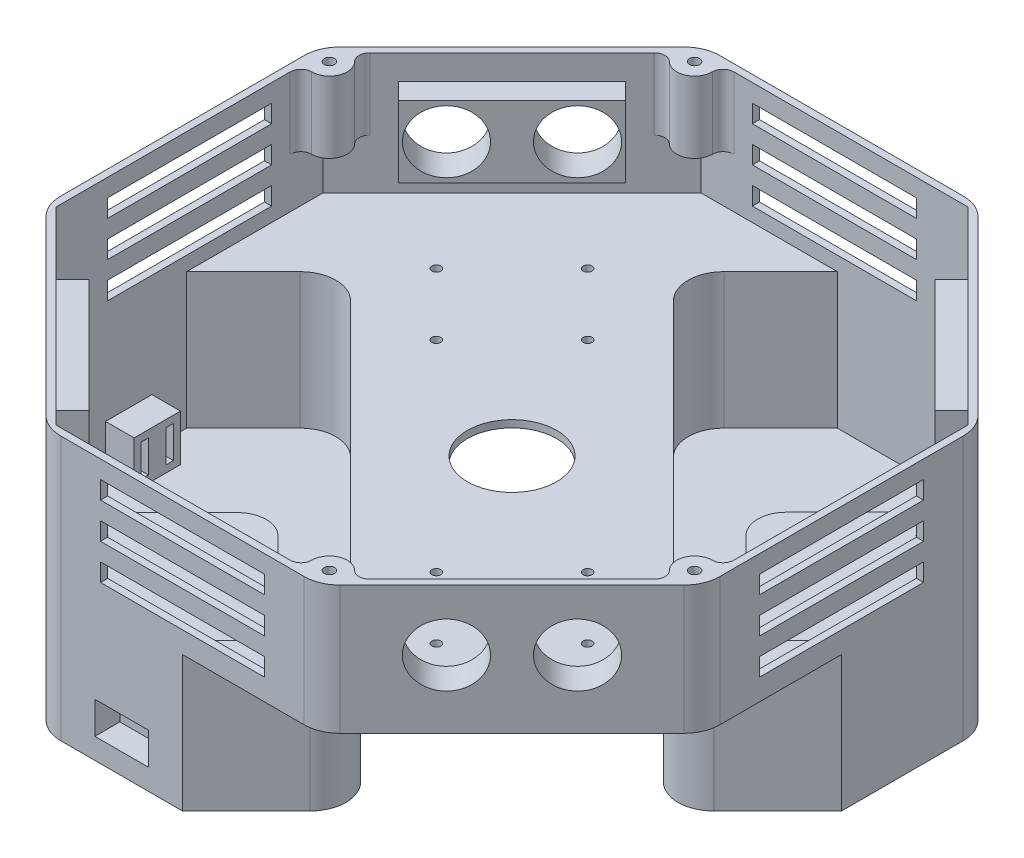
SolidWorks part; units mm, degrees
ref_plane "Front Plane" through (0, 0, 0) normal (0, 0, 1) x (1, 0, 0)
ref_plane "Top Plane" through (0, 0, 0) normal (0, 1, 0) x (1, 0, 0)
ref_plane "Right Plane" through (0, 0, 0) normal (1, 0, 0) x (0, 0, -1)
sketch "Sketch1" plane through (0, 0, 0) normal (0, 1, 0) x (1, 0, 0)
  line L7 (92.388, -38.2683) -> (92.388, 38.2683)
  line L8 (92.388, 38.2683) -> (38.2683, 92.388)
  line L9 (38.2683, 92.388) -> (-38.2683, 92.388)
  line L10 (-38.2683, 92.388) -> (-92.388, 38.2683)
  line L11 (-92.388, 38.2683) -> (-92.388, -38.2683)
  line L12 (-92.388, -38.2683) -> (-38.2683, -92.388)
  line L13 (-38.2683, -92.388) -> (38.2683, -92.388)
  line L14 (38.2683, -92.388) -> (92.388, -38.2683)
  circle A0 centre (0, 0) radius 92.388 construction
  dimension "D1" = 200
sketch "Sketch2" plane through (0, 0, 0) normal (0, 0, 1) x (1, 0, 0)
  line L0 (0, 0) -> (0, 74)
  point P3 (0, 61)
  point P4 (0, 41)
  point P5 (0, 38)
  point P10 (0, 71)
  dimension "D1" = 38
  dimension "D2" = 3
  dimension "D3" = 20
  dimension "D4" = 10
  dimension "D5" = 3
extrude "Boss-Extrude1" add sketch "Sketch1" along normal up to vertex (74 mm away) contours L13 L14 L7 L8 L9 L10 L11 L12 up to point (0, 74, 0)
sketch "Sketch3" plane through (0, 0, 0) normal (0, -1, 0) x (1, 0, 0)
  line L0 (-86.5414, -44.1149) -> (44.1149, 86.5414)
  line L1 (-38.2683, -92.388) -> (-92.388, -38.2683) construction
  line L2 (38.2683, 92.388) -> (92.388, 38.2683) construction
  line L3 (-44.1149, -86.5414) -> (86.5414, 44.1149)
  line L4 (-65.3281, -65.3281) -> (65.3281, 65.3281) construction
  line L5 (-86.5414, -44.1149) -> (-44.1149, -86.5414)
  line L6 (44.1149, 86.5414) -> (86.5414, 44.1149)
  dimension "D1" = 60
extrude "Cut-Extrude1" cut sketch "Sketch3" against normal blind 38
sketch "Sketch4" plane through (0, 0, 0) normal (0, -1, 0) x (1, 0, 0)
  line L0 (-92.388, -38.2683) -> (-86.5414, -44.1149) construction
  line L1 (-86.5414, -44.1149) -> (44.1149, 86.5414) construction
  line L2 (44.1149, 86.5414) -> (38.2683, 92.388) construction
  line L3 (38.2683, 92.388) -> (-38.2683, 92.388) construction
  line L4 (-38.2683, 92.388) -> (-92.388, 38.2683) construction
  line L5 (-92.388, 38.2683) -> (-92.388, -38.2683) construction
  line L6 (92.388, 38.2683) -> (86.5414, 44.1149) construction
  line L7 (86.5414, 44.1149) -> (-44.1149, -86.5414) construction
  line L8 (-44.1149, -86.5414) -> (-38.2683, -92.388) construction
  line L9 (-38.2683, -92.388) -> (38.2683, -92.388) construction
  line L10 (38.2683, -92.388) -> (92.388, -38.2683) construction
  line L11 (92.388, -38.2683) -> (92.388, 38.2683) construction
  line L12 (-92.388, -38.2683) -> (-86.5414, -44.1149)
  line L13 (-86.5414, -44.1149) -> (44.1149, 86.5414)
  line L14 (44.1149, 86.5414) -> (38.2683, 92.388)
  line L15 (38.2683, 92.388) -> (-38.2683, 92.388)
  line L16 (-38.2683, 92.388) -> (-92.388, 38.2683)
  line L17 (-92.388, 38.2683) -> (-92.388, -38.2683)
  line L18 (92.388, 38.2683) -> (86.5414, 44.1149)
  line L19 (86.5414, 44.1149) -> (-44.1149, -86.5414)
  line L20 (-44.1149, -86.5414) -> (-38.2683, -92.388)
  line L21 (-38.2683, -92.388) -> (38.2683, -92.388)
  line L22 (38.2683, -92.388) -> (92.388, -38.2683)
  line L23 (92.388, -38.2683) -> (92.388, 38.2683)
extrude "Cut-Extrude2" [suppressed] cut sketch "Sketch4" against normal blind 38
sketch "Sketch5" plane through (0, 0, 0) normal (0, -1, 0) x (1, 0, 0)
  line L12 (-49.0647, 70.2779) -> (-49.0647, 27.8515) construction
  line L13 (53.3073, -74.5205) -> (74.5205, -53.3073)
  line L14 (74.5205, -44.8221) -> (53.3073, -23.6088)
  line L15 (44.8221, -23.6088) -> (23.6088, -44.8221)
  line L16 (23.6088, -53.3073) -> (44.8221, -74.5205)
  line L17 (38.2683, -92.388) -> (92.388, -38.2683) construction
  line L18 (65.3281, -65.3281) -> (21.2132, -21.2132) construction
  line L19 (86.5414, 44.1149) -> (-44.1149, -86.5414) construction
  line L20 (65.3281, 65.3281) -> (-65.3281, -65.3281) construction
  line L21 (86.5414, 44.1149) -> (44.1149, 86.5414) construction
  line L22 (-86.5414, -44.1149) -> (-44.1149, -86.5414) construction
  line L23 (53.3073, -23.6088) -> (74.5205, -44.8221)
  line L24 (44.8221, -74.5205) -> (23.6088, -53.3073)
  line L25 (-65.3281, 65.3281) -> (-21.2132, 21.2132) construction
  line L26 (-74.5205, 44.8221) -> (-53.3073, 23.6088)
  line L27 (-23.6088, 53.3073) -> (-44.8221, 74.5205)
  line L28 (-53.3073, 23.6088) -> (-74.5205, 44.8221)
  line L29 (-23.6088, 44.8221) -> (-44.8221, 23.6088)
  line L30 (-44.8221, 74.5205) -> (-23.6088, 53.3073)
  line L31 (-74.5205, 53.3073) -> (-53.3073, 74.5205)
  line L32 (49.0647, -27.8515) -> (49.0647, -70.2779) construction
  arc A0 (44.8221, -74.5205) -> (53.3073, -74.5205) centre (49.0647, -70.2779) ccw
  arc A1 (74.5205, -53.3073) -> (74.5205, -44.8221) centre (70.2779, -49.0647) ccw
  arc A2 (53.3073, -23.6088) -> (44.8221, -23.6088) centre (49.0647, -27.8515) ccw
  arc A3 (23.6088, -44.8221) -> (23.6088, -53.3073) centre (27.8515, -49.0647) ccw
  arc A4 (44.8221, -23.6088) -> (53.3073, -23.6088) centre (49.0647, -27.8515) cw
  arc A5 (23.6088, -53.3073) -> (23.6088, -44.8221) centre (27.8515, -49.0647) cw
  arc A6 (53.3073, -74.5205) -> (44.8221, -74.5205) centre (49.0647, -70.2779) cw
  arc A7 (74.5205, -44.8221) -> (74.5205, -53.3073) centre (70.2779, -49.0647) cw
  arc A8 (-44.8221, 74.5205) -> (-53.3073, 74.5205) centre (-49.0647, 70.2779) ccw
  arc A9 (-74.5205, 53.3073) -> (-74.5205, 44.8221) centre (-70.2779, 49.0647) ccw
  arc A10 (-53.3073, 23.6088) -> (-44.8221, 23.6088) centre (-49.0647, 27.8515) ccw
  arc A11 (-23.6088, 44.8221) -> (-23.6088, 53.3073) centre (-27.8515, 49.0647) ccw
  arc A12 (-44.8221, 23.6088) -> (-53.3073, 23.6088) centre (-49.0647, 27.8515) cw
  arc A13 (-23.6088, 53.3073) -> (-23.6088, 44.8221) centre (-27.8515, 49.0647) cw
  arc A14 (-53.3073, 74.5205) -> (-44.8221, 74.5205) centre (-49.0647, 70.2779) cw
  arc A15 (-74.5205, 44.8221) -> (-74.5205, 53.3073) centre (-70.2779, 49.0647) cw
  point P12 (49.0647, -78.7632)
  point P15 (78.7632, -49.0647)
  point P20 (19.3662, -49.0647)
  point P41 (-49.0647, 19.3662)
  point P42 (-49.0647, 78.7632)
  point P43 (-78.7632, 49.0647)
  point P44 (43.2707, -43.2707)
  dimension "D4" = 6
  dimension "D1" = 42
  dimension "D2" = 42
  dimension "D5" = 5.794
extrude "Cut-Extrude3" cut sketch "Sketch5" against normal blind 8 contours L29 A11 L27 A8 L31 A9 L26 A10 region at (-49.0647, 0, 49.0647)
sketch "Sketch6" plane through (0, 38, 0) normal (0, -1, 0) x (1, 0, 0)
  line L0 (65.3281, 65.3281) -> (-65.3281, -65.3281)
  line L1 (86.5414, 44.1149) -> (44.1149, 86.5414) construction
  line L2 (-86.5414, -44.1149) -> (-44.1149, -86.5414) construction
sketch "Sketch7" plane through (0, 8, 0) normal (0, -1, 0) x (1, 0, 0)
  line L0 (-63.9139, 63.9139) -> (65.3281, -65.3281)
  line L1 (-74.5205, 53.3073) -> (-53.3073, 74.5205) construction
  line L2 (38.2683, -92.388) -> (92.388, -38.2683) construction
sketch "Sketch8" plane through (0, 0, 0) normal (0, -1, 0) x (1, 0, 0)
  line L0 (53.3073, -74.5205) -> (74.5205, -53.3073) construction
  line L1 (44.8221, -23.6088) -> (23.6088, -44.8221) construction
  line L2 (23.6088, -53.3073) -> (44.8221, -74.5205) construction
  line L3 (74.5205, -44.8221) -> (53.3073, -23.6088) construction
  line L4 (53.3073, -74.5205) -> (74.5205, -53.3073)
  line L5 (44.8221, -23.6088) -> (23.6088, -44.8221)
  line L6 (23.6088, -53.3073) -> (44.8221, -74.5205)
  line L7 (74.5205, -44.8221) -> (53.3073, -23.6088)
  arc A0 (74.5205, -53.3073) -> (74.5205, -44.8221) centre (70.2779, -49.0647) ccw construction
  arc A1 (44.8221, -74.5205) -> (53.3073, -74.5205) centre (49.0647, -70.2779) ccw construction
  arc A2 (23.6088, -44.8221) -> (23.6088, -53.3073) centre (27.8515, -49.0647) ccw construction
  arc A3 (53.3073, -23.6088) -> (44.8221, -23.6088) centre (49.0647, -27.8515) ccw construction
  arc A4 (74.5205, -53.3073) -> (74.5205, -44.8221) centre (70.2779, -49.0647) ccw
  arc A5 (44.8221, -74.5205) -> (53.3073, -74.5205) centre (49.0647, -70.2779) ccw
  arc A6 (23.6088, -44.8221) -> (23.6088, -53.3073) centre (27.8515, -49.0647) ccw
  arc A7 (53.3073, -23.6088) -> (44.8221, -23.6088) centre (49.0647, -27.8515) ccw
  point P12 (-29.9728, 51.186)
  point P13 (0, 32.0941)
  point P15 (-51.186, 29.9728)
  point P17 (-46.9434, 68.1566)
  point P19 (-68.1566, 46.9434)
extrude "Cut-Extrude4" cut sketch "Sketch8" against normal blind 8.1
sketch "Sketch9" plane through (0, 0, 0) normal (0, -1, 0) x (1, 0, 0)
  line L0 (0, 92.388) -> (92.388, 0)
  line L1 (38.2683, 92.388) -> (-38.2683, 92.388) construction
  line L2 (92.388, -38.2683) -> (92.388, 38.2683) construction
  line L3 (92.388, 0) -> (117.9869, 25.599)
  line L4 (117.9869, 25.599) -> (39.2649, 104.3211)
  line L5 (39.2649, 104.3211) -> (0, 92.388)
  line L6 (0, -92.388) -> (-92.388, 0)
  line L7 (-38.2683, -92.388) -> (38.2683, -92.388) construction
  line L8 (-92.388, 38.2683) -> (-92.388, -38.2683) construction
  line L9 (-92.388, 0) -> (-117.9869, -25.599)
  line L10 (-117.9869, -25.599) -> (-25.599, -117.9869)
  line L11 (-25.599, -117.9869) -> (0, -92.388)
extrude "Cut-Extrude5" cut sketch "Sketch9" against normal up to surface (38 mm away) up to face at (0, 38, 0)
shell "Shell2" thickness 2 removed face at (0, 74, 0)
sketch "Sketch10" plane through (63.9139, 0, -63.9139) normal (-0.7071, 0, 0.7071) x (0.7071, 0, 0.7071)
  line L0 (0, 67) -> (0, 47) construction
  line L1 (-22.5, 47) -> (22.5, 47) construction
  line L2 (-22.5, 47) -> (-22.5, 67) construction
  line L3 (-22.5, 67) -> (22.5, 67) construction
  line L4 (22.5, 47) -> (22.5, 67) construction
  line L5 (-22.5, 47) -> (22.5, 67) construction
  line L6 (-22.5, 67) -> (22.5, 47) construction
  line L7 (25.9975, 74.2342) -> (25.9975, 39.7658) construction
  line L8 (-37.4399, 74) -> (-37.4399, 40) construction
  line L9 (-37.4399, 74) -> (-37.4399, 2) construction
  line L10 (-63.3281, 40) -> (63.3281, 40) construction
  line L11 (-37.4399, 74) -> (37.4399, 74) construction
  circle A0 centre (13, 57) radius 8.75
  circle A1 centre (-13, 57) radius 8.75
  point P0 (0, 57)
  point P13 (25.9975, 57)
  point P15 (-37.4399, 57)
  point P16 (0, 74)
  dimension "D3" = 17.5
  dimension "D1" = 20
  dimension "D2" = 45
  dimension "D4" = 26
sketch "Sketch11" plane through (63.9139, 0, -63.9139) normal (-0.7071, 0, 0.7071) x (0.7071, 0, 0.7071)
  line L0 (-22.5, 47) -> (22.5, 47) construction
  line L1 (22.5, 47) -> (22.5, 67) construction
  line L2 (-22.5, 67) -> (22.5, 67) construction
  line L3 (-22.5, 47) -> (-22.5, 67) construction
  line L4 (-22.5, 47) -> (22.5, 47)
  line L5 (22.5, 47) -> (22.5, 67)
  line L6 (-22.5, 67) -> (22.5, 67)
  line L7 (-22.5, 47) -> (-22.5, 67)
extrude "Boss-Extrude2" add sketch "Sketch11" along normal blind 6.5
sketch "Sketch12" plane through (59.3177, 0, -59.3177) normal (-0.7071, 0, 0.7071) x (0.7071, 0, 0.7071)
  circle A0 centre (-13, 57) radius 8.75 construction
  circle A1 centre (13, 57) radius 8.75 construction
  circle A2 centre (-13, 57) radius 8.75
  circle A3 centre (13, 57) radius 8.75
extrude "Cut-Extrude6" cut sketch "Sketch12" against normal through all contours A2 | A3 region at (50.1254, 57, -68.5101)
mirror "Mirror1" about plane through (0, 0, 0) normal (1, 0, 0) of "Cut-Extrude6", "Boss-Extrude2"
mirror "Mirror2" about plane through (0, 0, 0) normal (0, 0, 1) of "Mirror1"
sketch "Sketch13" plane through (0, 74, 0) normal (0, 1, 0) x (1, 0, 0)
  line L0 (-37.4399, 90.388) -> (37.4399, -90.388) construction
  line L1 (38.2683, -92.388) -> (92.388, -38.2683) construction
  circle A1 centre (36.1973, -87.388) radius 5
  circle A2 centre (0, 0) radius 25.9051 construction
  circle A3 centre (-36.1973, -87.388) radius 5 construction
  circle A4 centre (-87.388, -36.1973) radius 5 construction
  circle A5 centre (-87.388, 36.1973) radius 5
  circle A6 centre (-36.1973, 87.388) radius 5
  circle A7 centre (36.1973, 87.388) radius 5 construction
  circle A8 centre (87.388, 36.1973) radius 5 construction
  circle A9 centre (87.388, -36.1973) radius 5
  point P26 (0, 0)
  dimension "D1" = 10
  dimension "D2" = 8
extrude "Boss-Extrude3" add sketch "Sketch13" against normal blind 20
fillet "Fillet2" radius 3 8 edges at (-86.6808, 64, -41.147) (32.1973, 64, 90.388) (41.147, 64, 86.6808) (86.6808, 64, 41.147) (90.388, 64, 32.1973) (-41.147, 64, -86.6808) (-32.1973, 64, -90.388) (-90.388, 64, -32.1973)
sketch "Sketch14" plane through (0, 74, 0) normal (0, 1, 0) x (1, 0, 0)
  point P0 (-87.388, 36.1973)
  point P1 (-36.1973, 87.388)
  point P3 (36.1973, -87.388)
  point P5 (87.388, -36.1973)
hole_wizard "M3.5x0.6 Tapped Hole1" positions "Sketch14" profile "Sketch15" tap size "M3.5x0.6" standard "ANSI Metric"
sketch "Sketch15" plane through (-87.388, 74, -36.1973) normal (1, 0, 0) x (0, 0, 1)
  line L0 (0, 0) -> (0, 10.8712)
  line L1 (0, 10.8712) -> (1.45, 10)
  line L2 (1.45, 10) -> (1.45, 0)
  line L5 (1.45, 0) -> (0, 0)
  line L10 (0, 10.8712) -> (-1.45, 10) construction
  line L11 (0, -6.35) -> (0, 107.95) construction
  dimension "Tap Drill Dia." = 2.9
  dimension "Tap Drill Depth" = 10
  dimension "Drill Angle" = 118
cosmetic thread "Hole Thread1" parameters "D1"=7, "D2"=3.5
cosmetic thread "Hole Thread2" parameters "D1"=7, "D2"=3.5
cosmetic thread "Hole Thread3" parameters "D1"=7, "D2"=3.5
cosmetic thread "Hole Thread4" parameters "D1"=7, "D2"=3.5
fillet "Fillet5" radius 10 12 edges at (38.2683, 37, -92.388) (92.388, 37, -38.2683) (92.388, 56, 38.2683) (38.2683, 56, 92.388) (-38.2683, 56, -92.388) (-92.388, 56, -38.2683) (-92.388, 37, 38.2683) (-38.2683, 37, 92.388) (-67.4072, 19, -24.9808) (-24.9808, 19, -67.4072) (67.4072, 19, 24.9808) (24.9808, 19, 67.4072)
sketch "Sketch16" plane through (0, 0, 0) normal (0, -1, 0) x (1, 0, 0)
  line L0 (41.1973, -89.459) -> (-0.8882, -43.3146)
  line L1 (-17.9097, -60.3361) -> (60.3361, 17.9097) construction
  line L2 (-0.8882, -43.3146) -> (23.6088, -44.8221)
  line L3 (23.6088, -44.8221) -> (21.2132, -21.2132)
  line L4 (-17.9097, -60.3361) -> (60.3361, 17.9097) construction
  line L5 (21.2132, -21.2132) -> (44.8221, -23.6088)
  line L6 (44.8221, -23.6088) -> (47.7588, 5.3324)
  line L7 (47.7588, 5.3324) -> (89.6938, -27.298)
  arc A0 (89.459, -41.1973) -> (92.388, -34.1262) centre (82.388, -34.1262) ccw construction
sketch "Sketch17" plane through (0, 0, 0) normal (0, -1, 0) x (1, 0, 0)
  line L0 (24.1702, -78.2018) -> (31.2413, -85.2729) construction
  line L1 (31.2413, -85.2729) -> (38.3123, -78.2018) construction
  line L2 (38.3123, -78.2018) -> (31.2413, -71.1307) construction
  line L3 (31.2413, -71.1307) -> (24.1702, -78.2018) construction
  line L4 (41.1973, -89.459) -> (-0.8882, -43.3146) construction
  line L5 (38.2683, -92.388) -> (92.388, -38.2683) construction
  line L6 (31.2413, -68.3023) -> (21.3418, -78.2018) construction
  line L7 (21.3418, -78.2018) -> (31.2413, -88.1013) construction
  line L8 (31.2413, -88.1013) -> (41.1408, -78.2018) construction
  line L9 (41.1408, -78.2018) -> (31.2413, -68.3023) construction
  line L10 (-63.9139, 63.9139) -> (65.3281, -65.3281) construction
  line L11 (-63.9139, 63.9139) -> (65.3281, -65.3281) construction
  line L12 (71.1307, -31.2413) -> (78.2018, -24.1702) construction
  line L13 (78.2018, -38.3123) -> (71.1307, -31.2413) construction
  line L14 (85.2729, -31.2413) -> (78.2018, -38.3123) construction
  line L15 (78.2018, -24.1702) -> (85.2729, -31.2413) construction
  line L16 (78.2018, -41.1408) -> (68.3023, -31.2413)
  line L17 (88.1013, -31.2413) -> (78.2018, -41.1408)
  line L18 (78.2018, -21.3418) -> (88.1013, -31.2413)
  line L19 (68.3023, -31.2413) -> (78.2018, -21.3418)
  point P2 (27.7057, -74.6663)
  dimension "D1" = 10
  dimension "D2" = 10
  dimension "D3" = 10
  dimension "D4" = 2
extrude "Boss-Extrude4" add sketch "Sketch17" against normal blind 8
sketch "Sketch18" plane through (0, 0, 0) normal (0, -1, 0) x (1, 0, 0)
  line L0 (78.2018, -22.756) -> (69.7165, -31.2413)
  line L1 (69.7165, -31.2413) -> (78.2018, -39.7266)
  line L2 (78.2018, -39.7266) -> (86.6871, -31.2413)
  line L3 (86.6871, -31.2413) -> (78.2018, -22.756)
  line L4 (68.3023, -31.2413) -> (78.2018, -41.1408)
  line L5 (78.2018, -21.3418) -> (68.3023, -31.2413)
  line L6 (88.1013, -31.2413) -> (78.2018, -21.3418)
  line L7 (78.2018, -41.1408) -> (88.1013, -31.2413)
  line L8 (68.3023, -31.2413) -> (78.2018, -41.1408) construction
  line L9 (78.2018, -21.3418) -> (68.3023, -31.2413) construction
  line L10 (88.1013, -31.2413) -> (78.2018, -21.3418) construction
  line L11 (78.2018, -41.1408) -> (88.1013, -31.2413) construction
  dimension "D1" = 0
  dimension "D2" = 1
extrude "Cut-Extrude7" cut sketch "Sketch18" against normal blind 5
sketch "Sketch19" plane through (0, 5, 0) normal (0, -1, 0) x (1, 0, 0)
  line L0 (71.1307, -32.6555) -> (79.616, -24.1702)
  line L1 (85.2729, -29.8271) -> (76.7876, -38.3123)
  line L2 (79.616, -24.1702) -> (78.2018, -22.756)
  line L3 (76.7876, -38.3123) -> (78.2018, -39.7266)
  line L4 (86.6871, -31.2413) -> (78.2018, -22.756)
  line L5 (78.2018, -22.756) -> (69.7165, -31.2413)
  line L6 (69.7165, -31.2413) -> (78.2018, -39.7266)
  line L7 (78.2018, -39.7266) -> (86.6871, -31.2413)
  line L8 (86.6871, -31.2413) -> (85.2729, -29.8271)
  line L9 (78.2018, -22.756) -> (69.7165, -31.2413)
  line L10 (69.7165, -31.2413) -> (71.1307, -32.6555)
  line L11 (78.2018, -39.7266) -> (86.6871, -31.2413)
  dimension "D1" = 0
  dimension "D2" = 2
  dimension "D3" = 2
extrude "Cut-Extrude8" cut sketch "Sketch19" against normal through all
sketch "Sketch20" plane through (-65.3281, 0, 65.3281) normal (-0.7071, 0, 0.7071) x (0.7071, 0, 0.7071)
  line L0 (-38.2683, 0) -> (38.2683, 0) construction
  circle A0 centre (21.8233, 23.5) radius 8.5 construction
  circle A1 centre (21.8233, 23.5) radius 5.5 construction
  circle A2 centre (21.8233, 23.5) radius 10.5
  point P2 (21.8233, 15)
  dimension "D1" = 15
  dimension "D2" = 17
  dimension "D3" = 11
  dimension "D4" = 2
extrude "Boss-Extrude5" add sketch "Sketch20" against normal blind 6
sketch "Sketch21" plane through (-65.3281, 0, 65.3281) normal (-0.7071, 0, 0.7071) x (0.7071, 0, 0.7071)
  circle A0 centre (21.8233, 23.5) radius 8.5 construction
  circle A1 centre (21.8233, 23.5) radius 8.5
extrude "Cut-Extrude9" cut sketch "Sketch21" against normal blind 3
sketch "Sketch22" plane through (-63.2068, 0, 63.2068) normal (-0.7071, 0, 0.7071) x (0.7071, 0, 0.7071)
  circle A0 centre (21.8233, 23.5) radius 5.5 construction
  circle A1 centre (21.8233, 23.5) radius 5.5
extrude "Cut-Extrude10" cut sketch "Sketch22" against normal blind 3
sketch "Sketch23" plane through (65.3281, 0, -65.3281) normal (0.7071, 0, -0.7071) x (-0.7071, 0, -0.7071)
  arc A0 (-21.75, 32.0046) -> (20.5971, 32.0046) centre (-0.5764, 27.0304) ccw
  arc A1 (-21.75, 32.0046) -> (20.5971, 32.0046) centre (-0.5764, 52.4388) ccw
  circle A2 centre (-13, 57) radius 8.75 construction
  circle A3 centre (-13, 57) radius 8.75 construction
  circle A4 centre (13, 57) radius 8.75 construction
  point P8 (-21.75, 57)
  point P10 (20.5971, 61.3412)
extrude "Cut-Extrude11" cut sketch "Sketch23" against normal blind 0.5
sketch "Sketch24" plane through (-65.3281, 0, 65.3281) normal (-0.7071, 0, 0.7071) x (0.7071, 0, 0.7071)
  circle A0 centre (-18.9113, 18.5) radius 5.25
  point P0 (21.8233, 23.5)
  dimension "D1" = 10.5
extrude "Boss-Extrude6" add sketch "Sketch24" against normal blind 11
sketch "Sketch25" plane through (-65.3281, 0, 65.3281) normal (-0.7071, 0, 0.7071) x (0.7071, 0, 0.7071)
  circle A0 centre (-18.9113, 18.5) radius 3.25
  circle A1 centre (-18.9113, 18.5) radius 5.25
  circle A2 centre (-18.9113, 18.5) radius 5.25 construction
  dimension "D2" = 2
  dimension "D1" = 0
extrude "Cut-Extrude12" cut sketch "Sketch25" against normal blind 8
sketch "Sketch26" plane through (-59.6713, 0, 59.6713) normal (-0.7071, 0, 0.7071) x (0.7071, 0, 0.7071)
  line L1 (-20.2999, 21.4384) -> (-20.2999, 15.5616)
  line L4 (-17.5228, 21.4384) -> (-17.5228, 15.5616)
  circle A3 centre (-18.9113, 18.5) radius 3.25 construction
  arc A4 (-20.2999, 21.4384) -> (-20.2999, 15.5616) centre (-18.9113, 18.5) ccw
  arc A5 (-17.5228, 15.5616) -> (-17.5228, 21.4384) centre (-18.9113, 18.5) ccw
extrude "Cut-Extrude13" cut sketch "Sketch26" against normal blind 6
sketch "Sketch29" plane through (0, 8, 0) normal (0, -1, 0) x (1, 0, 0)
  point P20 (68.1566, -46.9434)
  point P23 (51.186, -29.9728)
  point P26 (29.9728, -51.186)
  point P29 (46.9434, -68.1566)
  point P32 (-51.186, 29.9728)
  point P35 (-68.1566, 46.9434)
  point P38 (-29.9728, 51.186)
  point P41 (-46.9434, 68.1566)
  point P44 (0, 0)
hole_wizard "M3x0.5 Tapped Hole1" positions "Sketch29" profile "Sketch30" tap size "M3x0.5" standard "ANSI Metric"
cosmetic thread "Hole Thread7" parameters "D1"=64, "D2"=3
cosmetic thread "Hole Thread8" parameters "D1"=64, "D2"=3
cosmetic thread "Hole Thread9" parameters "D1"=64, "D2"=3
cosmetic thread "Hole Thread10" parameters "D1"=64, "D2"=3
cosmetic thread "Hole Thread11" parameters "D1"=64, "D2"=3
cosmetic thread "Hole Thread12" parameters "D1"=64, "D2"=3
sketch "Sketch30" plane through (68.1566, 8, -46.9434) normal (1, 0, 0) x (0, 0, -1)
  line L0 (0, 0) -> (0, 2.8511)
  line L1 (0, 2.8511) -> (1.25, 2.1)
  line L2 (1.25, 2.1) -> (1.25, 0)
  line L5 (1.25, 0) -> (0, 0)
  line L10 (0, 2.8511) -> (-1.25, 2.1) construction
  line L11 (0, -6.35) -> (0, 107.95) construction
  dimension "Tap Drill Dia." = 2.5
  dimension "Tap Drill Depth" = 2.1
  dimension "Drill Angle" = 118
cosmetic thread "Hole Thread21" parameters "D1"=64, "D2"=3
cosmetic thread "Hole Thread22" parameters "D1"=64, "D2"=3
sketch "Sketch31" plane through (0, 38, 0) normal (0, -1, 0) x (1, 0, 0)
  line L0 (-43.7426, -86.9137) -> (86.9137, 43.7426)
  line L1 (-86.9137, -43.7426) -> (43.7426, 86.9137)
  line L2 (-86.9137, -43.7426) -> (-43.7426, -86.9137)
  line L3 (43.7426, 86.9137) -> (86.9137, 43.7426)
  line L4 (34.9226, 56.1358) -> (56.1358, 34.9226) construction
  line L5 (-86.9137, -43.7426) -> (86.9137, 43.7426) construction
  line L6 (45.5292, 45.5292) -> (65.3281, 65.3281) construction
  line L7 (-89.459, 41.1973) -> (-41.1973, 89.459) construction
  line L8 (89.459, 41.1973) -> (41.1973, 89.459) construction
  line L9 (-21.5855, 21.5855) -> (21.5855, -21.5855) construction
  circle A2 centre (34.9226, 56.1358) radius 1.74
  circle A3 centre (56.1358, 34.9226) radius 1.74
  circle A4 centre (17.5984, 38.8116) radius 1.74
  circle A5 centre (38.8116, 17.5984) radius 1.74
  circle A6 centre (-56.1358, -34.9226) radius 1.74
  circle A7 centre (-34.9226, -56.1358) radius 1.74
  circle A8 centre (-17.5984, -38.8116) radius 1.74
  circle A9 centre (-38.8116, -17.5984) radius 1.74
  point P4 (65.3281, 65.3281)
  point P5 (45.5292, 45.5292)
  point P14 (0, 0)
  dimension "D10" = 3.48
  dimension "D2" = 2
  dimension "D3" = 28
  dimension "D4" = 0
  dimension "D6" = 15.5266
  dimension "D9" = 30
sketch "Sketch32" plane through (0, 38, 0) normal (0, -1, 0) x (1, 0, 0)
  point P0 (-56.1358, -34.9226)
  point P1 (-38.8116, -17.5984)
  point P3 (-17.5984, -38.8116)
  point P5 (-34.9226, -56.1358)
  point P7 (38.8116, 17.5984)
  point P9 (56.1358, 34.9226)
  point P11 (34.9226, 56.1358)
  point P13 (17.5984, 38.8116)
hole_wizard "M3x0.5 Tapped Hole2" positions "Sketch32" profile "Sketch33" tap size "M3x0.5" standard "ANSI Metric" end condition through all
sketch "Sketch33" plane through (-56.1358, 38, -34.9226) normal (1, 0, 0) x (0, 0, -1)
  line L0 (0, 0) -> (0, 36)
  line L1 (0, 36) -> (1.25, 36)
  line L2 (1.25, 36) -> (1.25, 0)
  line L5 (1.25, 0) -> (0, 0)
  line L11 (0, -6.35) -> (0, 107.95) construction
  dimension "Thru Tap Drill Dia." = 2.5
  dimension "Thru Tap Drill Depth" = 36
cosmetic thread "Hole Thread13" parameters "D2"=3
cosmetic thread "Hole Thread14" parameters "D2"=3
cosmetic thread "Hole Thread15" parameters "D2"=3
cosmetic thread "Hole Thread16" parameters "D2"=3
cosmetic thread "Hole Thread17" parameters "D2"=3
cosmetic thread "Hole Thread18" parameters "D2"=3
cosmetic thread "Hole Thread19" parameters "D2"=3
cosmetic thread "Hole Thread20" parameters "D2"=3
sketch "Sketch34" plane through (0, 38, 0) normal (0, -1, 0) x (1, 0, 0)
  circle A1 centre (0, 0) radius 12.5
  dimension "D1" = 25
extrude "Cut-Extrude14" cut sketch "Sketch34" against normal through all
sketch "Sketch35" plane through (92.388, 0, 0) normal (1, 0, 0) x (0, 0, -1)
  line L0 (0, 37.0336) -> (0, 90.07) construction
  line L1 (-23, 59) -> (23, 59)
  line L2 (-23, 64) -> (23, 64)
  line L3 (-23, 64) -> (-23, 69)
  line L4 (-23, 69) -> (23, 69)
  line L5 (23, 64) -> (23, 69)
  line L6 (-23, 64) -> (23, 69) construction
  line L7 (-23, 69) -> (23, 64) construction
  line L8 (-23, 54) -> (-23, 59)
  line L9 (-23, 54) -> (23, 54)
  line L10 (23, 54) -> (23, 59)
  line L11 (-23, 59) -> (23, 54) construction
  line L12 (-23, 54) -> (23, 59) construction
  line L13 (-23, 49) -> (23, 49)
  line L14 (-23, 44) -> (-23, 49)
  line L15 (-23, 44) -> (23, 44)
  line L16 (23, 44) -> (23, 49)
  line L17 (-23, 49) -> (23, 44) construction
  line L18 (-23, 44) -> (23, 49) construction
  line L19 (90.388, 74) -> (-90.388, 74) construction
  line L20 (17.9097, 0) -> (17.9097, 38) construction
  line L21 (-65.3281, 38) -> (65.3281, 38) construction
  line L22 (7.9097, 21.25) -> (27.9097, 21.25) construction
  line L23 (7.9097, 28.75) -> (27.9097, 28.75) construction
  line L24 (7.9097, 28.75) -> (7.9097, 31.75) construction
  line L25 (7.9097, 31.75) -> (27.9097, 31.75) construction
  line L26 (27.9097, 28.75) -> (27.9097, 31.75) construction
  line L27 (7.9097, 28.75) -> (27.9097, 31.75) construction
  line L28 (7.9097, 31.75) -> (27.9097, 28.75) construction
  line L29 (7.9097, 24.25) -> (27.9097, 24.25) construction
  line L30 (27.9097, 21.25) -> (27.9097, 24.25) construction
  line L31 (7.9097, 21.25) -> (7.9097, 24.25) construction
  line L32 (7.9097, 24.25) -> (27.9097, 21.25) construction
  line L33 (7.9097, 21.25) -> (27.9097, 24.25) construction
  line L34 (7.9097, 13.75) -> (27.9097, 13.75) construction
  line L35 (7.9097, 16.75) -> (27.9097, 16.75) construction
  line L36 (27.9097, 13.75) -> (27.9097, 16.75) construction
  line L37 (7.9097, 13.75) -> (7.9097, 16.75) construction
  line L38 (7.9097, 16.75) -> (27.9097, 13.75) construction
  line L39 (7.9097, 13.75) -> (27.9097, 16.75) construction
  line L40 (7.9097, 6.25) -> (27.9097, 6.25) construction
  line L41 (7.9097, 9.25) -> (27.9097, 9.25) construction
  line L42 (27.9097, 6.25) -> (27.9097, 9.25) construction
  line L43 (7.9097, 6.25) -> (7.9097, 9.25) construction
  line L44 (7.9097, 9.25) -> (27.9097, 6.25) construction
  line L45 (7.9097, 6.25) -> (27.9097, 9.25) construction
  line L46 (27.9097, 21.25) -> (27.9097, 16.75) construction
  point P2 (0, 66.5)
  point P23 (17.9097, 30.25)
  point P29 (17.9097, 19)
  point P41 (27.9097, 19)
  dimension "D1" = 46
  dimension "D2" = 5
  dimension "D3" = 5
  dimension "D4" = 3
  dimension "D5" = 20
  dimension "5" = 5
  dimension "D8" = 5
  dimension "D6" = 4
extrude "Cut-Extrude15" cut sketch "Sketch35" against normal up to next
ref_plane "Plane1" through (0, 0, 0) normal (0.7071, 0, 0.7071) x (0.7071, 0, -0.7071)
mirror "Mirror3" about plane through (0, 0, 0) normal (0.7071, 0, 0.7071) of "Cut-Extrude15"
ref_plane "Plane2" through (0, 0, 0) normal (-0.7071, 0, 0.7071) x (0.7071, 0, 0.7071)
mirror "Mirror4" about plane through (0, 0, 0) normal (-0.7071, 0, 0.7071) of "Mirror3", "Cut-Extrude15"
sketch "Sketch37" plane through (0, 0, 92.388) normal (0, 0, 1) x (1, 0, 0)
  line L0 (-17.0631, 0) -> (-17.0631, 38.9532) construction
  line L1 (-23.5631, 6.8582) -> (-10.5631, 6.8582) construction
  line L2 (-23.5631, 6.8582) -> (-23.5631, 13.8582) construction
  line L3 (-23.5631, 13.8582) -> (-10.5631, 13.8582) construction
  line L4 (-10.5631, 6.8582) -> (-10.5631, 13.8582) construction
  line L5 (-23.5631, 6.8582) -> (-10.5631, 13.8582) construction
  line L6 (-23.5631, 13.8582) -> (-10.5631, 6.8582) construction
  line L7 (-34.1262, 0) -> (0, 0) construction
  line L8 (-26.5631, 3.8582) -> (-26.5631, 16.8582)
  line L9 (-26.5631, 16.8582) -> (-7.5631, 16.8582)
  line L10 (-7.5631, 3.8582) -> (-7.5631, 16.8582)
  line L11 (-26.5631, 3.8582) -> (-7.5631, 3.8582)
  point P0 (-17.0631, 10.3582)
  dimension "D1" = 13
  dimension "D2" = 7
  dimension "D3" = 3
extrude "Boss-Extrude7" add sketch "Sketch37" against normal blind 9
sketch "Sketch38" plane through (0, 0, 92.388) normal (0, 0, 1) x (1, 0, 0)
  line L0 (-9.5631, 14.8582) -> (-24.5631, 14.8582)
  line L1 (-24.5631, 14.8582) -> (-24.5631, 5.8582)
  line L2 (-24.5631, 5.8582) -> (-9.5631, 5.8582)
  line L3 (-9.5631, 5.8582) -> (-9.5631, 14.8582)
  line L4 (-26.5631, 16.8582) -> (-26.5631, 3.8582)
  line L5 (-7.5631, 16.8582) -> (-26.5631, 16.8582)
  line L6 (-7.5631, 3.8582) -> (-7.5631, 16.8582)
  line L7 (-26.5631, 3.8582) -> (-7.5631, 3.8582)
  line L8 (-26.5631, 16.8582) -> (-26.5631, 3.8582) construction
  line L9 (-7.5631, 16.8582) -> (-26.5631, 16.8582) construction
  line L10 (-7.5631, 3.8582) -> (-7.5631, 16.8582) construction
  line L11 (-26.5631, 3.8582) -> (-7.5631, 3.8582) construction
  dimension "D1" = 0
  dimension "D2" = 2
extrude "Cut-Extrude16" cut sketch "Sketch38" against normal blind 7
sketch "Sketch39" plane through (0, 0, 85.388) normal (0, 0, 1) x (1, 0, 0)
  line L0 (-24.5631, 10.3582) -> (-9.5631, 10.3582) construction
  line L1 (-24.5631, 14.8582) -> (-24.5631, 5.8582) construction
  line L2 (-9.5631, 5.8582) -> (-9.5631, 14.8582) construction
  line L4 (-24.5631, 8.8582) -> (-9.5631, 8.8582)
  line L5 (-24.5631, 8.8582) -> (-24.5631, 11.8582)
  line L6 (-24.5631, 11.8582) -> (-9.5631, 11.8582)
  line L7 (-9.5631, 8.8582) -> (-9.5631, 11.8582)
  line L8 (-24.5631, 8.8582) -> (-9.5631, 11.8582) construction
  line L9 (-24.5631, 11.8582) -> (-9.5631, 8.8582) construction
  point P6 (-17.0631, 10.3582)
  dimension "D1" = 3
extrude "Cut-Extrude17" cut sketch "Sketch39" against normal up to next
sketch "Sketch40" plane through (-92.388, 0, 0) normal (-1, 0, 0) x (0, 0, 1)
  line L0 (17.0631, 0) -> (17.0631, 24.8704) construction
  line L1 (0, 0) -> (34.1262, 0) construction
  line L2 (10.5631, 2) -> (23.5631, 2)
  line L3 (13.5631, 5) -> (20.5631, 5) construction
  line L4 (13.5631, 5) -> (13.5631, 12) construction
  line L5 (13.5631, 12) -> (20.5631, 12) construction
  line L6 (20.5631, 5) -> (20.5631, 12) construction
  line L7 (13.5631, 5) -> (20.5631, 12) construction
  line L8 (13.5631, 12) -> (20.5631, 5) construction
  line L9 (23.5631, 2) -> (23.5631, 15)
  line L10 (10.5631, 15) -> (23.5631, 15)
  line L11 (10.5631, 2) -> (10.5631, 15)
  point P4 (17.0631, 8.5)
  dimension "D1" = 7
  dimension "D2" = 7
  dimension "D3" = 5
  dimension "D4" = 3
extrude "Boss-Extrude8" add sketch "Sketch40" against normal blind 10
sketch "Sketch41" plane through (-92.388, 0, 0) normal (-1, 0, 0) x (0, 0, 1)
  line L0 (21.5631, 4) -> (21.5631, 13)
  line L1 (21.5631, 13) -> (12.5631, 13)
  line L2 (12.5631, 13) -> (12.5631, 4)
  line L3 (12.5631, 4) -> (21.5631, 4)
  line L4 (10.5631, 2) -> (23.5631, 2)
  line L5 (23.5631, 2) -> (23.5631, 15)
  line L6 (23.5631, 15) -> (10.5631, 15)
  line L7 (10.5631, 15) -> (10.5631, 2)
  line L8 (10.5631, 2) -> (23.5631, 2) construction
  line L9 (23.5631, 2) -> (23.5631, 15) construction
  line L10 (23.5631, 15) -> (10.5631, 15) construction
  line L11 (10.5631, 15) -> (10.5631, 2) construction
  dimension "D1" = 0
  dimension "D2" = 2
extrude "Cut-Extrude18" cut sketch "Sketch41" against normal blind 7
sketch "Sketch42" plane through (-85.388, 0, 0) normal (-1, 0, 0) x (0, 0, 1)
  line L0 (12.5631, 4) -> (21.5631, 4) construction
  line L1 (12.5631, 13) -> (14.5631, 13)
  line L2 (12.5631, 13) -> (12.5631, 4)
  line L3 (12.5631, 4) -> (14.5631, 4)
  line L4 (14.5631, 13) -> (14.5631, 4)
  line L5 (12.5631, 4) -> (21.5631, 4) construction
  line L6 (21.5631, 13) -> (19.5631, 13)
  line L7 (21.5631, 13) -> (21.5631, 4)
  line L8 (21.5631, 4) -> (19.5631, 4)
  line L9 (19.5631, 13) -> (19.5631, 4)
  dimension "D1" = 2
  dimension "D2" = 2
extrude "Cut-Extrude19" cut sketch "Sketch42" against normal up to next
fillet "Fillet6" radius 10 4 edges at (67.4072, 21, 22.1523) (22.1523, 21, 67.4072) (-67.4072, 21, -22.1523) (-22.1523, 21, -67.4072)
equation "\"across_flat\"= 200"
equation "\"D1@Sketch1\"=\"across_flat\""
equation "\"motor_groove\"=38"
equation "\"thickness_1\"= 3"
equation "\"thickness_2\"=2"
equation "\"D1@Sketch2\"=\"motor_groove\""
equation "\"D2@Sketch2\"=\"thickness_1\""
equation "\"battery_holder_height\"= 20"
equation "\"D3@Sketch2\"=\"battery_holder_height\""
equation "\"gen_allowance\"= 10"
equation "\"D4@Sketch2\"=\"gen_allowance\""
equation "\"D5@Sketch2\"=\"thickness_1\""
equation "\"motor_width\"= 60"
equation "\"D1@Sketch3\"=\"motor_width\""
equation "\"D1@Cut-Extrude1\"=\"motor_groove\""
equation "\"D1@Cut-Extrude2\"=\"motor_groove\""
equation "\"castor_breadth\"= 52 - 10"
equation "\"D1@Sketch5\"=\"castor_breadth\""
equation "\"castor_length\"= 52 - 10"
equation "\"D2@Sketch5\"=\"castor_length\""
equation "\"castor_groove\"=8"
equation "\"D1@Cut-Extrude3\"=\"castor_groove\""
equation "\"D1@Cut-Extrude4\"=\"castor_groove\" + 0.1"
equation "\"D1@Shell2\"=\"thickness_2\""
equation "\"ultrasonic_groove\"= 14"
equation "\"D1@Boss-Extrude2\"=\"ultrasonic_groove\" - 2.5* \"thickness_1\""
equation "\"fillet1\"=3"
equation "\"D1@Fillet2\"=\"fillet1\""
equation "\"D1@Boss-Extrude4\"=2 * \"thickness_1\" + 2"
equation "\"D1@Cut-Extrude7\"=\"thickness_1\"+2"
equation "\"D1@Cut-Extrude12\"=11-3"
